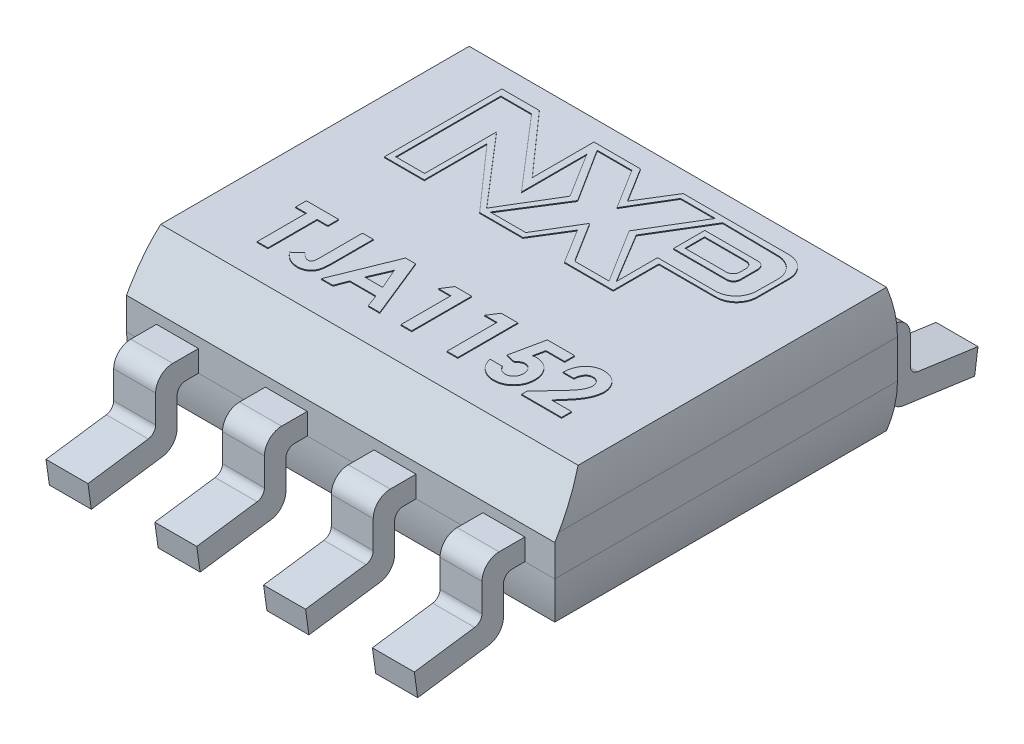
SolidWorks part; units mm, degrees
ref_plane "Front Plane" through (0, 0, 0) normal (0, 0, 1) x (1, 0, 0)
ref_plane "Top Plane" through (0, 0, 0) normal (0, 1, 0) x (1, 0, 0)
ref_plane "Right Plane" through (0, 0, 0) normal (1, 0, 0) x (0, 0, -1)
sketch "Sketch1" plane through (0, 0, 0) normal (0, 1, 0) x (1, 0, 0)
  line L1 (-2.5, 2) -> (2.5, 2)
  line L2 (-2.5, 2) -> (-2.5, -2)
  line L3 (-2.5, -2) -> (2.5, -2)
  line L4 (2.5, 2) -> (2.5, -2)
  line L5 (-2.5, 2) -> (2.5, -2) construction
  line L6 (-2.5, -2) -> (2.5, 2) construction
  point P0 (0, 0)
  dimension "D1" = 5
  dimension "D2" = 4
extrude "Boss-Extrude1" add sketch "Sketch1" along normal blind 1.45
sketch "Sketch2" plane through (-2.5, 0, 0) normal (-1, 0, 0) x (0, 0, 1)
  line L0 (2, 0.8687) -> (1.6644, 1.45)
  line L1 (2, 1.45) -> (2, 0) construction
  line L2 (-2, 1.45) -> (2, 1.45) construction
  line L3 (0, 0) -> (0, 0.828) construction
  line L4 (-2, 0.725) -> (-1.3983, 0.725) construction
  line L6 (-2, 1.45) -> (-2, 0) construction
  line L7 (-1.8644, 1.6723) -> (-2.1559, 1.6723)
  line L8 (-2.1559, 1.6723) -> (-2.1559, 0.954)
  line L9 (-2.1559, 0.954) -> (-2, 0.9484)
  line L10 (-2, 0.5016) -> (-2.1559, 0.5016)
  line L11 (-2.1559, 0.5016) -> (-2.1559, -0.2223)
  line L12 (-2.1559, -0.2223) -> (-1.8644, -0.2223)
  line L13 (1.6644, 1.45) -> (1.6644, 1.7317)
  line L14 (1.6644, 1.7317) -> (2.4871, 1.7317)
  line L15 (2.4871, 1.7317) -> (2.4871, 0.8687)
  line L16 (2.4871, 0.8687) -> (2, 0.8687)
  line L17 (2, 0.5015) -> (2.4871, 0.5015)
  line L18 (2.4871, 0.5015) -> (2.4871, -0.2223)
  line L19 (2.4871, -0.2223) -> (1.8644, -0.2223)
  arc A0 (2, 0.5015) -> (1.8644, -0.2223) centre (0, 0.5015) cw
  arc A1 (-2, 0.5016) -> (-1.8644, -0.2223) centre (0, 0.5015) ccw
  arc A2 (-2, 0.9484) -> (-1.8644, 1.6723) centre (0, 0.9485) cw
  dimension "D1" = 2
  dimension "D2" = 60
extrude "Cut-Extrude1" cut sketch "Sketch2" against normal blind 61.45
sketch "Sketch5" plane through (0, 0, -2) normal (0, 0, -1) x (-1, 0, 0)
  line L1 (0, 1.45) -> (0, 1.0867) construction
  line L2 (-3.4587, 0.725) -> (-2.857, 0.725) construction
  line L3 (-2.3644, 1.6723) -> (-2.6559, 1.6723)
  line L4 (-2.6559, 1.6723) -> (-2.6559, 0.954)
  line L5 (-2.6559, 0.954) -> (-2.5, 0.9484)
  line L6 (-2.5, 0.5016) -> (-2.6559, 0.5016)
  line L7 (-2.6559, 0.5016) -> (-2.6559, -0.2223)
  line L8 (-2.6559, -0.2223) -> (-2.3644, -0.2223)
  line L16 (2.5, 1.45) -> (-2.5, 1.45) construction
  line L17 (-2.6559, 1.6723) -> (-2.3644, 1.6723)
  line L18 (-2.6559, 0.9484) -> (-2.6559, 1.6723)
  line L19 (-2.5, 0.9484) -> (-2.6559, 0.9484)
  line L20 (-2.6559, 0.496) -> (-2.5, 0.5016)
  line L21 (-2.6559, -0.2223) -> (-2.6559, 0.496)
  line L22 (-2.3644, -0.2223) -> (-2.6559, -0.2223)
  line L23 (2.6559, -0.2223) -> (2.3644, -0.2223)
  line L24 (2.6559, 0.5016) -> (2.6559, -0.2223)
  line L25 (2.5, 0.5016) -> (2.6559, 0.5016)
  line L26 (2.6559, 0.954) -> (2.5, 0.9484)
  line L27 (2.6559, 1.6723) -> (2.6559, 0.954)
  line L28 (2.3644, 1.6723) -> (2.6559, 1.6723)
  arc A1 (-2.5, 0.5016) -> (-2.3644, -0.2223) centre (-0.5, 0.5015) ccw
  arc A2 (-2.5, 0.9484) -> (-2.3644, 1.6723) centre (-0.5, 0.9485) cw
  arc A3 (-2.5, 0.5016) -> (-2.3644, -0.2223) centre (-0.5, 0.5015) ccw
  arc A4 (-2.5, 0.9484) -> (-2.3644, 1.6723) centre (-0.5, 0.9485) cw
  arc A5 (2.5, 0.5016) -> (2.3644, -0.2223) centre (0.5, 0.5015) cw
  arc A6 (2.5, 0.9484) -> (2.3644, 1.6723) centre (0.5, 0.9485) ccw
extrude "Cut-Extrude2" cut sketch "Sketch5" against normal blind 61.45 contours L5 A2 L3 L4 | A1 L20 L7 L22 | A6 L26 L27 L28 | L25 A5 L23 L24
sketch "Sketch6" plane through (-2.5, 0, 0) normal (-1, 0, 0) x (0, 0, 1)
  line L5 (1.9361, 0) -> (-1.9361, 0) construction
  line L7 (0, 0) -> (0, -0.7239) construction
  line L8 (2.2535, 0.75) -> (2.3, 0.75)
  line L9 (2.5, 0.55) -> (2.5, 0.2276)
  line L10 (2.5, 0.1406) -> (3.25, 0.1406) construction
  line L11 (3.25, 0.1406) -> (3.25, -0.1094) construction
  line L12 (3.25, -0.1094) -> (2.25, -0.1094) construction
  line L13 (2.25, 0.0645) -> (2.25, 0.4)
  line L14 (2.25, 0.5) -> (2.2535, 0.5)
  line L15 (-3.25, -0.1094) -> (-2.25, -0.1094) construction
  line L17 (2.4222, -0.1335) -> (3.2508, -0.25)
  line L18 (2.5861, 0.1286) -> (3.2901, 0.0296)
  line L19 (3.2508, -0.25) -> (3.2901, 0.0296)
  line L20 (-3.25, 0.1406) -> (-3.25, -0.1094) construction
  line L21 (-2.5, 0.1406) -> (-3.25, 0.1406) construction
  line L22 (-3.2508, -0.25) -> (-3.2901, 0.0296)
  line L23 (-2.5861, 0.1286) -> (-3.2901, 0.0296)
  line L24 (-2.4222, -0.1335) -> (-3.2508, -0.25)
  line L25 (-2.25, 0.5) -> (-2.2535, 0.5)
  line L26 (-2.25, 0.0645) -> (-2.25, 0.4)
  line L27 (-2.5, 0.55) -> (-2.5, 0.2276)
  line L28 (-2.2535, 0.75) -> (-2.3, 0.75)
  line L29 (-2.15, 0.5) -> (2.15, 0.5)
  line L30 (-2.2535, 0.75) -> (2.2535, 0.75)
  arc A0 (2.4222, -0.1335) -> (2.25, 0.0645) centre (2.45, 0.0645) cw
  arc A1 (2.5, 0.55) -> (2.3, 0.75) centre (2.3, 0.55) ccw
  arc A2 (2.5861, 0.1286) -> (2.5, 0.2276) centre (2.6, 0.2276) cw
  arc A3 (2.25, 0.4) -> (2.15, 0.5) centre (2.15, 0.4) ccw
  arc A4 (-2.25, 0.4) -> (-2.15, 0.5) centre (-2.15, 0.4) cw
  arc A5 (-2.5861, 0.1286) -> (-2.5, 0.2276) centre (-2.6, 0.2276) ccw
  arc A6 (-2.5, 0.55) -> (-2.3, 0.75) centre (-2.3, 0.55) cw
  arc A7 (-2.4222, -0.1335) -> (-2.25, 0.0645) centre (-2.45, 0.0645) ccw
  dimension "D9" = 0.2
  dimension "D10" = 0.1
  dimension "D4" = 0.25
  dimension "D5" = 0.25
  dimension "D6" = 1
  dimension "D7" = 8
  dimension "D8" = 0.25
extrude "Boss-Extrude2" add sketch "Sketch6" against normal up to surface (5 mm away) up to face at (2.5, 0.8431, 0.3908)
sketch "Sketch7" plane through (0, 1.45, 0) normal (0, 1, 0) x (1, 0, 0)
  line L0 (2.5, -2) -> (-2.5, -2) construction
  line L1 (-2.5, -2) -> (-2.15, -2)
  line L2 (-2.5, -2) -> (-2.5, -3.534)
  line L3 (-2.5, -3.534) -> (-2.15, -3.534)
  line L4 (-2.15, -2) -> (-2.15, -3.534)
  line L5 (-1.66, -2) -> (-0.88, -2)
  line L6 (-1.66, -2) -> (-1.66, -3.6106)
  line L7 (-1.66, -3.6106) -> (-0.88, -3.6106)
  line L8 (-0.88, -2) -> (-0.88, -3.6106)
  line L9 (0, 0) -> (-3.4858, 0) construction
  line L10 (-0.39, -2) -> (0.39, -2)
  line L11 (-0.39, -2) -> (-0.39, -3.6106)
  line L12 (-0.39, -3.6106) -> (0.39, -3.6106)
  line L13 (0.39, -2) -> (0.39, -3.6106)
  line L14 (2.5, -2) -> (2.15, -2)
  line L15 (2.5, -2) -> (2.5, -3.783)
  line L16 (2.5, -3.783) -> (2.15, -3.783)
  line L17 (2.15, -2) -> (2.15, -3.783)
  line L18 (1.66, -2) -> (0.88, -2)
  line L19 (1.66, -2) -> (1.66, -3.6776)
  line L20 (1.66, -3.6776) -> (0.88, -3.6776)
  line L21 (0.88, -2) -> (0.88, -3.6776)
  line L22 (0.88, 2) -> (0.88, 3.6776)
  line L23 (1.66, 3.6776) -> (0.88, 3.6776)
  line L24 (1.66, 2) -> (1.66, 3.6776)
  line L25 (1.66, 2) -> (0.88, 2)
  line L26 (2.15, 2) -> (2.15, 3.783)
  line L27 (2.5, 3.783) -> (2.15, 3.783)
  line L28 (2.5, 2) -> (2.5, 3.783)
  line L29 (2.5, 2) -> (2.15, 2)
  line L30 (0.39, 2) -> (0.39, 3.6106)
  line L31 (-0.39, 3.6106) -> (0.39, 3.6106)
  line L32 (-0.39, 2) -> (-0.39, 3.6106)
  line L33 (-0.39, 2) -> (0.39, 2)
  line L34 (-0.88, 2) -> (-0.88, 3.6106)
  line L35 (-1.66, 3.6106) -> (-0.88, 3.6106)
  line L36 (-1.66, 2) -> (-1.66, 3.6106)
  line L37 (-1.66, 2) -> (-0.88, 2)
  line L38 (-2.15, 2) -> (-2.15, 3.534)
  line L39 (-2.5, 3.534) -> (-2.15, 3.534)
  line L40 (-2.5, 2) -> (-2.5, 3.534)
  line L41 (-2.5, 2) -> (-2.15, 2)
  dimension "D1" = 0.49
  dimension "D2" = 0.49
  dimension "D3" = 0.49
  dimension "D4" = 0.49
  dimension "D5" = 0.78
  dimension "D6" = 0.78
  dimension "D7" = 0.78
  dimension "D8" = 0.35
extrude "Cut-Extrude3" cut sketch "Sketch7" against normal blind 61.45
sketch "Sketch8" plane through (0, 1.45, 0) normal (0, 1, 0) x (1, 0, 0)
  line L0 (70.6653, 255.7964) -> (518.6653, 255.7964) construction
  line L1 (-1.8034, 0.3139) -> (-1.8034, 1.6861)
  line L2 (-1.8034, 1.6861) -> (-1.3672, 1.6861)
  line L3 (-1.3672, 1.6861) -> (-0.7295, 0.965)
  line L4 (-0.7295, 0.965) -> (-0.7295, 1.6861)
  line L5 (-0.7295, 1.6861) -> (-0.186, 1.6861)
  line L6 (-0.186, 1.6861) -> (0.0636, 1.2836)
  line L7 (0.0636, 1.2836) -> (0.3123, 1.6861)
  line L8 (0.3123, 1.6861) -> (1.5487, 1.6861)
  line L9 (1.7887, 1.4461) -> (1.7887, 1.0732)
  line L10 (1.5487, 0.8332) -> (0.8817, 0.8332)
  line L11 (0.8817, 0.8332) -> (0.8817, 0.2999)
  line L12 (0.8817, 0.2999) -> (0.3123, 0.2999)
  line L13 (0.3123, 0.2999) -> (0.0636, 0.7007)
  line L14 (0.0636, 0.7007) -> (-0.1796, 0.3069)
  line L15 (-0.1796, 0.3069) -> (-0.6842, 0.3069)
  line L16 (-0.6842, 0.3069) -> (-1.3377, 1.046)
  line L17 (-1.3377, 1.046) -> (-1.3377, 0.3139)
  line L18 (-1.3377, 0.3139) -> (-1.8034, 0.3139)
  line L19 (-1.7377, 0.3801) -> (-1.7377, 1.6079)
  line L20 (-1.7377, 1.6079) -> (-1.3789, 1.6079)
  line L21 (-1.3789, 1.6079) -> (-0.6481, 0.759)
  line L22 (-0.6481, 0.759) -> (-0.6481, 1.5221)
  line L23 (-0.6481, 1.5221) -> (-0.3221, 0.9996)
  line L24 (-0.3221, 0.9996) -> (-0.6875, 0.3914)
  line L25 (-0.6875, 0.3914) -> (-1.3999, 1.219)
  line L26 (-1.3999, 1.219) -> (-1.3999, 0.3801)
  line L27 (-1.3999, 0.3801) -> (-1.7377, 0.3801)
  line L28 (-0.6279, 1.6222) -> (-0.2222, 1.6222)
  line L29 (-0.2222, 1.6222) -> (0.068, 1.1578)
  line L30 (0.068, 1.1578) -> (0.3464, 1.6222)
  line L31 (0.3464, 1.6222) -> (0.7514, 1.6222)
  line L32 (0.7514, 1.6222) -> (0.3743, 0.9932)
  line L33 (0.3743, 0.9932) -> (0.7643, 0.369)
  line L34 (0.7643, 0.369) -> (0.3619, 0.369)
  line L35 (0.3619, 0.369) -> (0.068, 0.8394)
  line L36 (0.068, 0.8394) -> (-0.2117, 0.373)
  line L37 (-0.2117, 0.373) -> (-0.6279, 0.373)
  line L38 (-0.6279, 0.373) -> (-0.2334, 0.9996)
  line L39 (-0.2334, 0.9996) -> (-0.6279, 1.6222)
  line L40 (0.8381, 1.6222) -> (1.4939, 1.613)
  line L41 (1.7305, 1.3696) -> (1.727, 1.1248)
  line L42 (1.4871, 0.8882) -> (0.8112, 0.8882)
  line L43 (0.8112, 0.8882) -> (0.8112, 0.4059)
  line L44 (0.8112, 0.4059) -> (0.4571, 0.9932)
  line L45 (0.4571, 0.9932) -> (0.8381, 1.6222)
  line L46 (0.8112, 1.4396) -> (1.433, 1.4396)
  line L47 (1.513, 1.3596) -> (1.513, 1.1532)
  line L48 (1.433, 1.0732) -> (0.8112, 1.0732)
  line L49 (0.8112, 1.4396) -> (0.8112, 1.0732)
  line L50 (0.8755, 1.3732) -> (1.3583, 1.3732)
  line L51 (0.8755, 1.3732) -> (0.8755, 1.144)
  line L52 (0.8755, 1.144) -> (1.3583, 1.144)
  line L53 (1.4383, 1.2932) -> (1.4383, 1.224)
  arc A0 (1.7887, 1.0732) -> (1.5487, 0.8332) centre (1.5487, 1.0732) cw
  arc A1 (1.5487, 1.6861) -> (1.7887, 1.4461) centre (1.5487, 1.4461) cw
  arc A2 (1.727, 1.1248) -> (1.4871, 0.8882) centre (1.4871, 1.1282) cw
  arc A3 (1.4939, 1.613) -> (1.7305, 1.3696) centre (1.4905, 1.373) cw
  arc A4 (1.3583, 1.144) -> (1.4383, 1.224) centre (1.3583, 1.224) ccw
  arc A5 (1.3583, 1.3732) -> (1.4383, 1.2932) centre (1.3583, 1.2932) cw
  arc A6 (1.513, 1.1532) -> (1.433, 1.0732) centre (1.433, 1.1532) cw
  arc A7 (1.433, 1.4396) -> (1.513, 1.3596) centre (1.433, 1.3596) cw
extrude "Boss-Extrude3" add sketch "Sketch8" along normal blind 0.01 contours A1 L8 L7 L6 L5 L4 L3 L2 L1 L18 L17 L16 L15 L14 L13 L12 L11 L10 A0 L9 L38 L39 L28 L29 L30 L31 L32 L33 L34 L35 L36 L37 L26 L27 L19 L20 L21 L22 L23 L24 L25 L40 A3 L41 A2 L42 L43 L44 | A7 L46 L49 L48 A6 L47 L50 A5 L53 A4 L52 L51
sketch "Sketch9" plane through (0, 1.45, 0) normal (0, 1, 0) x (1, 0, 0)
  line L0 (-1.8233, -1.2861) -> (2.2013, -1.2861) construction
  text T0 "<b>TJA1152</b>" font "Century Gothic" height 0.7
extrude "Boss-Extrude4" add sketch "Sketch9" along normal blind 0.01
